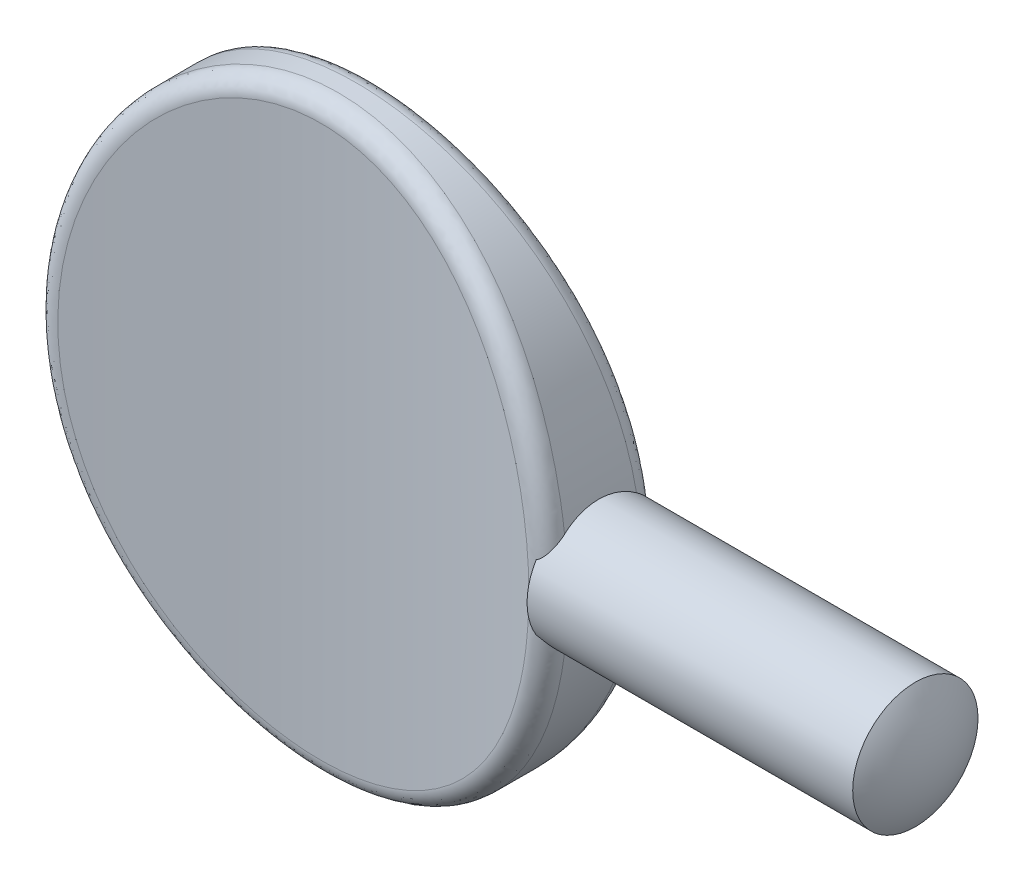
SolidWorks part; units mm, degrees
ref_plane "Front" through (0, 0, 0) normal (0, 0, 1) x (1, 0, 0)
ref_plane "Top" through (0, 0, 0) normal (0, 1, 0) x (1, 0, 0)
ref_plane "Right" through (0, 0, 0) normal (1, 0, 0) x (0, 0, -1)
ref_axis "Axis1" through (-50, 0, 0) along (1, 0, 0)
sketch "Sketch1" plane through (0, 0, 0) normal (0, 0, 1) x (1, 0, 0)
  line L0 (0, 0) -> (22.606, 0) construction
  line L1 (13.208, -2.413) -> (13.208, 2.413)
  line L2 (13.208, -2.413) -> (9.6776, -2.413) construction
  ellipse E0 centre (0, 0) end of major axis (0, -11.303) minor radius 9.906
  dimension "D2" = 3.302
  dimension "B" = 19.812
  dimension "L" = 12.7
extrude "Extrude1" add sketch "Sketch1" along normal mid plane 4.572
sketch "Sketch2" plane through (0, 0, 0) normal (0, 1, 0) x (1, 0, 0)
  line L0 (9.906, 2.286) -> (-9.906, 2.286) construction
  line L1 (0, 0) -> (0, 1.1721) construction
  line L2 (-1.7991, 0) -> (2.0444, 0) construction
  line L3 (-9.906, -2.286) -> (9.906, -2.286) construction
  line L6 (-9.906, 2.286) -> (-9.906, -2.286)
  line L7 (9.906, 2.286) -> (9.906, -2.286)
  arc A0 (-9.906, 2.286) -> (9.906, 2.286) centre (0, 40.2844) ccw
  arc A1 (-9.906, -2.286) -> (9.906, -2.286) centre (0, -40.2844) cw
extrude "Cut-Extrude1" cut sketch "Sketch2" against normal through all and the other way through all flip side to cut
fillet "Fillet3" radius 0.6773 2 edges at (-9.9037, -0.2444, 2.2854) (2.9825, 10.7785, -1.1294)
sketch "Sketch3" plane through (0, 0, 0) normal (0, 1, 0) x (1, 0, 0)
  line L0 (22.606, 0) -> (22.606, -2.4455) construction
  line L1 (0, 0) -> (21.0288, 0) construction
  line L2 (0, 0) -> (22.606, 0) construction
  line L3 (13.208, 2.413) -> (13.208, 0) construction
  line L4 (13.208, 2.413) -> (21.8792, 2.413)
  line L6 (13.208, 2.413) -> (9.3367, 2.413)
  line L7 (9.0722, 2.0783) -> (9.0722, 0)
  line L8 (9.3367, 0) -> (9.3367, 2.413) construction
  line L9 (9.0722, 0) -> (22.606, 0)
  arc A0 (9.3367, 2.413) -> (9.0722, 2.0783) centre (8.9927, 2.413) cw
  arc A1 (22.606, 0) -> (21.8792, 2.413) centre (18.2372, 0) ccw
  arc A3 (-9.906, 2.286) -> (9.906, 2.286) centre (0, 40.2844) ccw construction
revolve "Revolve1" add sketch "Sketch3" angle 360 about L0
cosmetic thread "Cosmetic Thread1" [suppressed]
sketch "Sketch4" plane through (0, 0, 0) normal (0, 0, 1) x (1, 0, 0)
  line L0 (0, 0) -> (27.7993, 0) construction
  line L1 (21.6958, 2.413) -> (21.8792, 2.0955)
  line L2 (21.8792, 2.0955) -> (22.0625, 2.413)
  line L3 (22.0625, 2.413) -> (22.0625, 2.7796)
  line L4 (22.0625, 2.7796) -> (21.6958, 2.7796)
  line L5 (21.6958, 2.7796) -> (21.6958, 2.413)
  line L6 (21.8792, 2.413) -> (21.8792, -2.413) construction
  dimension "D1" = 4.191
  dimension "D2" = 4.826
revolve "Cut-Revolve10" [suppressed] cut sketch "Sketch4" angle 360 about L0
pattern_linear "LPattern10" [suppressed] count 24 along (-1, 0, 0) of bodies 109
equation "\"D2@Sketch1\" = \"B@Sketch1\" / 6"
equation "\"D1@Fillet3\" = \"C1@Sketch2\" / 3"
equation "\"DIA@Sketch3\" = \"D@Sketch1\""
equation "\"D1@Sketch4\" = \"D2@Cosmetic Thread1\""
equation "\"D2@Sketch4\" = \"DIA@Sketch3\""
equation "\"D1@LPattern10\" = \"L@Sketch1\" / \"P@LPattern10\" - 1"
